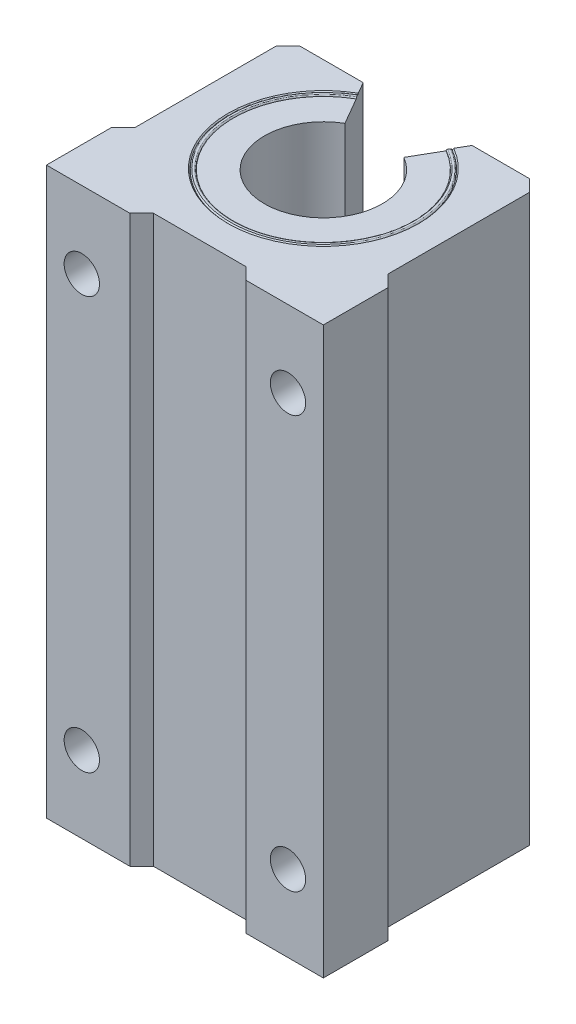
SolidWorks part; units mm, degrees
ref_plane "前视基准面" through (0, 0, 0) normal (0, 0, 1) x (1, 0, 0)
ref_plane "上视基准面" through (0, 0, 0) normal (0, 1, 0) x (1, 0, 0)
ref_plane "右视基准面" through (0, 0, 0) normal (1, 0, 0) x (0, 0, -1)
ref_plane "基准面1" through (0, -48, 0) normal (0, 1, 0) x (-1, 0, 0)
sketch "草图4" plane through (0, -48, 0) normal (0, 1, 0) x (-1, 0, 0)
  line L0 (7.8333, 21) -> (-7.8333, 21)
  line L1 (-7.8333, 21) -> (-7.8333, 23)
  line L2 (-7.8333, 23) -> (-23, 23)
  line L3 (-23, 23) -> (-23, 12)
  line L4 (-23, 12) -> (-21, 10)
  line L5 (-21, 10) -> (-21, -16)
  line L6 (-21, -16) -> (-9.2376, -16)
  line L7 (22, -16) -> (22, 10)
  line L8 (22, 10) -> (24, 12)
  line L9 (24, 12) -> (24, 23)
  line L10 (24, 23) -> (7.8333, 23)
  line L11 (7.8333, 23) -> (7.8333, 21)
  line L12 (9.2376, -16) -> (5, -8.6603)
  line L13 (-9.2376, -16) -> (-5, -8.6603)
  line L14 (49.0341, 0) -> (-54.8041, 0) construction
  line L15 (55, 0) -> (-55, 0) construction
  line L16 (0, 51.6133) -> (0, -47.1655) construction
  line L17 (0, 55) -> (0, -55) construction
  line L18 (9.2376, -16) -> (22, -16)
  arc A0 (5, -8.6603) -> (-5, -8.6603) centre (0, 0) ccw
  dimension "S" = 20
  dimension "D1" = 2
  dimension "W" = 47
  dimension "A" = 11
  dimension "G" = 39
  dimension "h2" = 23
  dimension "D6" = 135
  dimension "D7" = 135
  dimension "D" = 24
  dimension "D9" = 15.6667
  dimension "D10" = 7.8333
  dimension "D11" = 2
  dimension "D12" = 2
  dimension "D13" = 11
  dimension "θ" = 60
  dimension "D16" = 30
  dimension "h1" = 10
extrude "拉伸2" add sketch "草图4" along normal blind 96
chamfer "倒角1" distance 2 angle 45 2 edges at (-7.8333, 0, 23) (7.8333, 0, 23)
sketch "草图5" plane through (0, 0, 23) normal (0, 0, 1) x (1, 0, 0)
  line L0 (-18, 35) -> (17, 35) construction
  line L1 (17, 35) -> (17, -35) construction
  line L2 (17, -35) -> (-18, -35) construction
  line L3 (-18, -35) -> (-18, 35) construction
  line L4 (-0.5, 48) -> (-0.5, -48) construction
  line L7 (-18, -35) -> (17, -35)
  line L8 (23, 0) -> (-24, 0)
  line L9 (23, 48) -> (23, -48) construction
  line L10 (-24, 48) -> (-24, -48) construction
  line L11 (-24, 48) -> (23, 48) construction
  line L12 (-7.8333, -48) -> (7.8333, -48) construction
  circle A0 centre (-18, 35) radius 3
  circle A1 centre (17, 35) radius 3
  circle A2 centre (17, -35) radius 3
  circle A3 centre (-18, -35) radius 3
  dimension "D1" = 70
  dimension "S1" = 6
  dimension "D2" = 35
  dimension "D3" = 35
  dimension "D4" = 17.5
extrude "切除-拉伸1" cut sketch "草图5" against normal blind 12 contours A0 | A1 | A3 | A2 region at (-20.9151, -35, 23) region at (-18, 35, 23) region at (17, 35, 23)
chamfer "倒角2" distance 2 angle 45 2 edges at (-22, 0, -16) (21, 0, -16)
sketch "草图6" plane through (0, 0, 0) normal (1, 0, 0) x (0, 0, -1)
  line L0 (-16.2, -48) -> (-16, -47.8)
  line L1 (-23, -48) -> (-12, -48) construction
  line L2 (-15.45, -48) -> (0, -48)
  line L3 (-15.25, -47.8) -> (0, -47.8)
  line L4 (0, 25.85) -> (0, -25.85) construction
  line L5 (-16.2, -48) -> (-15.7988, -48)
  line L6 (-10, -48) -> (14, -48) construction
  line L7 (0, -48) -> (0, -47.8)
  line L8 (0, -10.2649) -> (0, -26.9155) construction
  arc A0 (-16, -47.8) -> (-15.7988, -48) centre (-15.7988, -47.7988) ccw
  arc A1 (-15.25, -47.8) -> (-15.45, -48) centre (-15.45, -47.8) cw
  dimension "D6" = 0.2
  dimension "D7" = 0.2012
  dimension "D1" = 30.5
  dimension "D2" = 45
  dimension "D3" = 0.2
  dimension "dL" = 32
revolve "切除-旋转1" cut sketch "草图6" angle 360 about L8
mirror "镜向1" about plane through (0, 0, 0) normal (0, 1, 0) of "切除-旋转1"
equation "\"D11@草图4\" = \"D1@草图4\""
equation "\"D12@草图4\" = \"D1@草图4\""
equation "\"D9@草图4\" = \"W@草图4\" / 3"
equation "\"D10@草图4\" = \"W@草图4\" / 6"
equation "\"D13@草图4\" = \"A@草图4\""
equation "\"D16@草图4\" = \"θ@草图4\" / 2"
equation "\"D1@基准面1\" = \"M@拉伸2\" / 2"
equation "\"D1@倒角1\" = \"D1@草图4\""
